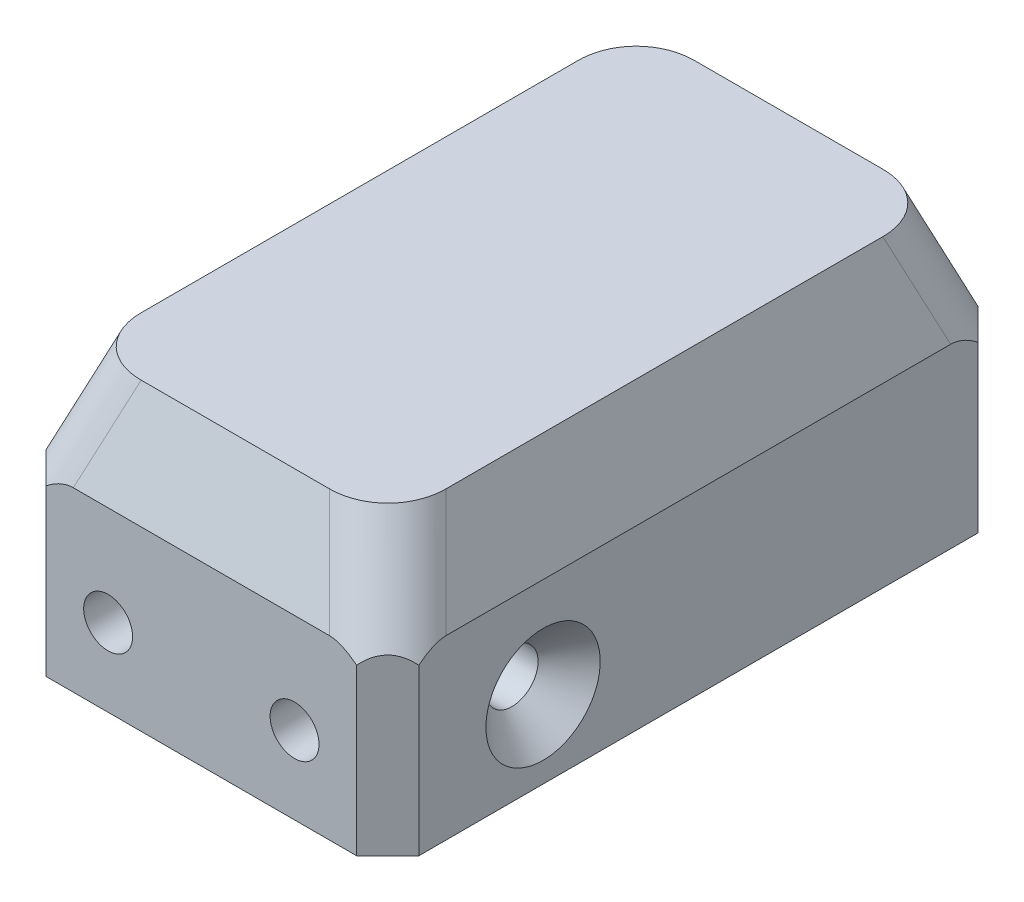
SolidWorks part; units mm, degrees
ref_plane "Front Plane" through (0, 0, 0) normal (0, 0, 1) x (1, 0, 0)
ref_plane "Top Plane" through (0, 0, 0) normal (0, 1, 0) x (1, 0, 0)
ref_plane "Right Plane" through (0, 0, 0) normal (1, 0, 0) x (0, 0, -1)
sketch "Sketch1" plane through (0, 0, 0) normal (0, 1, 0) x (1, 0, 0)
  line L0 (0, 12.7) -> (0, -12.7) construction
  line L1 (7.62, -12.7) -> (-7.62, -12.7)
  line L2 (7.62, -12.7) -> (7.62, 12.7)
  line L3 (7.62, 12.7) -> (-7.62, 12.7)
  line L4 (-7.62, -12.7) -> (-7.62, 12.7)
  line L5 (7.62, -12.7) -> (-7.62, 12.7) construction
  line L6 (7.62, 12.7) -> (-7.62, -12.7) construction
  line L7 (0, 0) -> (0, 12.7) construction
  line L8 (-7.62, 6.35) -> (7.62, 6.35) construction
  line L9 (0, 0) -> (0, -12.7) construction
  line L10 (-7.62, -6.35) -> (7.62, -6.35) construction
  line L11 (-7.62, 0) -> (7.62, 0) construction
  line L12 (3.81, 2.54) -> (-3.81, 2.54)
  line L13 (3.81, 2.54) -> (3.81, 10.16)
  line L14 (3.81, 10.16) -> (-3.81, 10.16)
  line L15 (-3.81, 2.54) -> (-3.81, 10.16)
  line L16 (3.81, 2.54) -> (-3.81, 10.16) construction
  line L17 (3.81, 10.16) -> (-3.81, 2.54) construction
  line L18 (3.81, -10.16) -> (-3.81, -10.16)
  line L19 (-3.81, -2.54) -> (-3.81, -10.16)
  line L20 (3.81, -2.54) -> (-3.81, -2.54)
  line L21 (3.81, -2.54) -> (3.81, -10.16)
  point P0 (0, 0)
  point P9 (0, 6.35)
  point P12 (0, 6.35)
  point P15 (0, -6.35)
  dimension "D1" = 25.4
  dimension "D2" = 15.24
  dimension "D3" = 7.62
  dimension "D4" = 7.62
extrude "Boss-Extrude1" add sketch "Sketch1" along normal blind 6.35 contours L2 L1 L4 L3 | L18 L19 L20 L21 | L13 L12 L15 L14
sketch "Sketch2" plane through (7.62, 0, 0) normal (1, 0, 0) x (0, 0, -1)
  line L0 (-12.7, 0) -> (0, 0) construction
  line L1 (-6.35, 0) -> (-6.35, 6.35) construction
  line L2 (-12.7, 6.35) -> (12.7, 6.35) construction
  line L3 (0, 0) -> (0, 6.35) construction
  circle A0 centre (-6.35, 3.175) radius 1.0668
  circle A1 centre (6.35, 3.175) radius 1.0668
  dimension "D1" = 2.1336
extrude "Cut-Extrude1" cut sketch "Sketch2" against normal through all
sketch "Sketch3" plane through (0, 0, 12.7) normal (0, 0, 1) x (1, 0, 0)
  line L0 (0, 0) -> (0, 6.35) construction
  line L1 (7.62, 6.35) -> (-7.62, 6.35) construction
  line L2 (-7.62, 6.35) -> (0, 6.35) construction
  line L3 (-3.81, 6.35) -> (-3.81, 0) construction
  line L4 (-3.81, 0) -> (0, 0) construction
  line L5 (-1.905, 0) -> (-1.905, 6.35) construction
  line L6 (-7.62, 4.2418) -> (-7.62, 2.1082) construction
  line L7 (-7.62, 4.2418) -> (-7.62, 2.1082) construction
  circle A0 centre (-1.905, 3.175) radius 1.0668
  circle A1 centre (1.905, 3.175) radius 1.0668
  dimension "D1" = 2.1336
extrude "Cut-Extrude2" cut sketch "Sketch3" against normal through all
sketch "Sketch4" plane through (0, 6.35, 0) normal (0, 1, 0) x (1, 0, 0)
  line L0 (-3.81, 2.54) -> (-3.81, -2.54)
  line L1 (-3.81, -2.54) -> (3.81, -2.54)
  line L2 (3.81, -2.54) -> (3.81, 2.54)
  line L3 (3.81, 2.54) -> (-3.81, 2.54)
extrude "Boss-Extrude2" add sketch "Sketch4" against normal up to surface (6.35 mm away) up to face at (0, 0, 6.35)
sketch "Sketch5" plane through (0, 0, 0) normal (0, -1, 0) x (1, 0, 0)
  line L0 (-3.81, -6.35) -> (-7.62, -6.35) construction
  line L1 (-3.81, -2.54) -> (-3.81, -10.16) construction
  line L2 (-7.62, 12.7) -> (-7.62, -12.7) construction
  line L3 (-3.81, -3.4925) -> (-3.81, -9.2075) construction
  point P9 (-3.81, -6.35)
  dimension "D1" = 5.715
sketch "Sketch6" plane through (0, 0, 12.7) normal (0, 0, 1) x (1, 0, 0)
  circle A0 centre (3.81, 3.175) radius 1
  circle A1 centre (-3.81, 3.175) radius 1
  dimension "D1" = 2
  dimension "D2" = 2
extrude "Cut-Extrude3" cut sketch "Sketch6" against normal up to surface (2.54 mm away) up to face at (-0.8382, 3.175, 10.16)
sketch "Sketch7" plane through (0, 0, 12.7) normal (0, 0, 1) x (1, 0, 0)
  line L0 (3.81, 4.175) -> (3.81, 2.175) construction
  arc A0 (2.8937, 3.5756) -> (2.8937, 2.7744) centre (1.905, 3.175) ccw construction
  arc A1 (-2.8937, 2.7744) -> (-2.8937, 3.5756) centre (-1.905, 3.175) ccw construction
  arc A2 (2.8937, 3.5756) -> (2.8937, 2.7744) centre (1.905, 3.175) ccw
  arc A3 (-2.8937, 2.7744) -> (-2.8937, 3.5756) centre (-1.905, 3.175) ccw
  arc A4 (2.8937, 3.5756) -> (2.8937, 2.7744) centre (3.81, 3.175) ccw
  arc A5 (-2.8937, 2.7744) -> (-2.8937, 3.5756) centre (-3.81, 3.175) ccw
extrude "Boss-Extrude3" add sketch "Sketch7" against normal up to surface (2.54 mm away) up to face at (0, 3.175, 10.16)
sketch "Sketch8" plane through (0, 0, -12.7) normal (0, 0, -1) x (-1, 0, 0)
  circle A0 centre (3.81, 3.175) radius 1 construction
  circle A1 centre (-3.81, 3.175) radius 1 construction
  circle A2 centre (3.81, 3.175) radius 1
  circle A3 centre (-3.81, 3.175) radius 1
extrude "Cut-Extrude4" cut sketch "Sketch8" against normal up to surface (2.54 mm away) up to face at (-0.8382, 3.175, -10.16)
sketch "Sketch9" plane through (0, 0, -12.7) normal (0, 0, -1) x (-1, 0, 0)
  line L0 (-3.81, 2.175) -> (-3.81, 4.175) construction
  line L1 (3.81, 2.175) -> (3.81, 4.175) construction
  arc A0 (2.8937, 3.5756) -> (2.8937, 2.7744) centre (1.905, 3.175) ccw construction
  arc A1 (-2.8937, 2.7744) -> (-2.8937, 3.5756) centre (-1.905, 3.175) ccw construction
  arc A2 (2.8937, 3.5756) -> (2.8937, 2.7744) centre (1.905, 3.175) ccw
  arc A3 (-2.8937, 2.7744) -> (-2.8937, 3.5756) centre (-1.905, 3.175) ccw
  arc A4 (-2.8937, 2.7744) -> (-2.8937, 3.5756) centre (-3.81, 3.175) ccw
  arc A5 (2.8937, 3.5756) -> (2.8937, 2.7744) centre (3.81, 3.175) ccw
extrude "Boss-Extrude4" add sketch "Sketch9" against normal up to surface (2.54 mm away) up to face at (0, 3.175, -10.16)
sketch "Sketch10" plane through (-7.62, 0, 0) normal (-1, 0, 0) x (0, 0, 1)
  circle A0 centre (-6.35, 3.175) radius 1.0668 construction
  circle A1 centre (-6.35, 3.175) radius 1.0668
extrude "Boss-Extrude5" add sketch "Sketch10" against normal up to surface (15.24 mm away) up to face at (7.62, 3.175, 5.2832)
sketch "Sketch11" plane through (0, 0, 0) normal (0, -1, 0) x (1, 0, 0)
  line L0 (3.81, -10.16) -> (-3.81, -10.16) construction
  line L1 (3.81, -2.54) -> (3.81, -10.16) construction
  line L2 (3.81, -2.54) -> (-3.81, -2.54) construction
  line L3 (-3.81, -2.54) -> (-3.81, -10.16) construction
  line L4 (3.81, -10.16) -> (-3.81, -10.16)
  line L5 (3.81, -2.54) -> (3.81, -10.16)
  line L6 (3.81, -2.54) -> (-3.81, -2.54)
  line L7 (-3.81, -2.54) -> (-3.81, -10.16)
extrude "Boss-Extrude6" add sketch "Sketch11" against normal up to surface (6.35 mm away) up to face at (0, 6.35, -6.35)
sketch "Sketch13" plane through (0, 6.35, 0) normal (0, 1, 0) x (1, 0, 0)
  line L0 (-15.1122, 3.7944) -> (-15.0451, -2.0493) construction
  line L1 (-15.06, 6.2006) -> (-15.06, 9.3807) construction
  line L2 (-3.81, -9.272) -> (-3.81, -3.428)
  line L4 (-3.81, -2.54) -> (-3.81, -10.16) construction
  line L5 (-3.81, -3.428) -> (-3.81, -1.0217) construction
  line L6 (-3.81, -1.0217) -> (-3.81, 2.1584) construction
  line L7 (-3.81, -2.1647) -> (-3.81, 3.3014)
  line L8 (-3.81, -2.1647) -> (3.81, -2.1647)
  line L9 (3.81, -2.1647) -> (3.81, 3.3014)
  line L10 (3.81, 3.3014) -> (-3.81, 3.3014)
  point P7 (-3.81, -6.35)
  point P10 (-3.81, -6.35)
  point P15 (-3.81, 0.5683)
  dimension "D1" = 5.8436
  dimension "D2" = 3.1801
  dimension "D3" = 2.4063
  dimension "D4" = 2.4063
  dimension "D5" = 1.143
extrude "Cut-Extrude5" cut sketch "Sketch13" against normal through all contours L9 L10 L7 L8 region at (0, 6.35, -0.5683)
fillet "Fillet1" radius 1.27 4 edges at (3.81, 3.175, 2.1647) (-3.81, 3.175, 2.1647) (-3.81, 3.175, 2.54) (3.81, 3.175, 2.54) conic rho 0.5
sketch "Sketch15" plane through (0, 6.35, 0) normal (0, 1, 0) x (1, 0, 0)
  line L0 (-2.54, -2.1647) -> (-2.54, -2.54)
  line L1 (-2.54, -2.54) -> (2.54, -2.54)
  line L2 (2.54, -2.54) -> (2.54, -2.1647)
  line L3 (2.54, -2.1647) -> (-2.54, -2.1647)
extrude "Cut-Extrude6" cut sketch "Sketch15" against normal through all
sketch "Sketch16" plane through (0, 0, 10.16) normal (0, 0, 1) x (1, 0, 0)
  line L1 (-3.81, 2.175) -> (-3.81, 4.175)
  line L2 (-3.81, 2.175) -> (-3.81, 4.175)
  line L3 (3.81, 4.175) -> (3.81, 2.175)
  line L4 (3.81, 4.175) -> (3.81, 2.175)
  arc A1 (-3.81, 4.175) -> (-3.81, 2.175) centre (-3.81, 3.175) ccw
  arc A2 (-3.81, 4.175) -> (-3.81, 2.175) centre (-3.81, 3.175) ccw
  arc A3 (3.81, 2.175) -> (3.81, 4.175) centre (3.81, 3.175) ccw
  arc A4 (3.81, 2.175) -> (3.81, 4.175) centre (3.81, 3.175) ccw
  dimension "D1" = 0
  dimension "D2" = 0
extrude "Cut-Extrude7" cut sketch "Sketch16" against normal blind 1.905
sketch "Sketch17" plane through (0, 6.35, 0) normal (0, 1, 0) x (1, 0, 0)
  line L0 (-3.81, -0.8947) -> (-3.81, -3.81) construction
  line L1 (-3.81, -3.81) -> (3.81, -3.81) construction
  line L2 (3.81, -3.81) -> (3.81, -0.8947) construction
  line L3 (3.81, -0.8947) -> (-3.81, -0.8947) construction
  line L4 (-2.54, -2.1647) -> (2.54, -2.1647)
  line L5 (2.54, -2.1647) -> (3.81, -2.1647)
  line L6 (3.81, -2.1647) -> (3.81, 3.3014)
  line L7 (3.81, 3.3014) -> (-3.81, 3.3014)
  line L8 (-3.81, 3.3014) -> (-3.81, -2.1647)
  line L9 (-3.81, -2.1647) -> (-2.54, -2.1647)
  line L10 (-4.1853, -2.54) -> (-2.54, -2.54)
  line L11 (-2.54, -2.54) -> (2.54, -2.54)
  line L12 (2.54, -2.54) -> (4.1853, -2.54)
  line L13 (4.1853, -2.54) -> (4.1853, 3.6767)
  line L14 (4.1853, 3.6767) -> (-4.1853, 3.6767)
  line L15 (-4.1853, 3.6767) -> (-4.1853, -2.54)
extrude "Boss-Extrude7" add sketch "Sketch17" along normal blind 3.175
sketch "Sketch18" plane through (0, 9.525, 0) normal (0, 1, 0) x (1, 0, 0)
  line L0 (-4.1853, 0.5683) -> (-3.81, 0.5683) construction
  line L1 (-3.81, 3.3014) -> (-3.81, -2.1647) construction
  line L2 (-3.81, 0.5683) -> (-4.826, 0.5683) construction
  line L3 (-4.8203, 4.3117) -> (-4.8203, -3.175)
  line L4 (-4.1853, 3.6767) -> (-4.1853, -2.54)
  line L5 (-4.1853, -2.54) -> (4.1853, -2.54)
  line L6 (4.1853, -2.54) -> (4.1853, 3.6767)
  line L7 (4.1853, 3.6767) -> (-4.1853, 3.6767)
  line L8 (-4.1853, 3.6767) -> (-4.1853, -2.54)
  line L9 (-4.1853, -2.54) -> (4.1853, -2.54)
  line L10 (4.1853, -2.54) -> (4.1853, 3.6767)
  line L11 (4.1853, 3.6767) -> (-4.1853, 3.6767)
  line L12 (-4.8203, -3.175) -> (4.8203, -3.175)
  line L13 (4.8203, -3.175) -> (4.8203, 4.3117)
  line L14 (4.8203, 4.3117) -> (-4.8203, 4.3117)
  dimension "D2" = 1.016
  dimension "D1" = 0
  dimension "D3" = 0.635
extrude "Boss-Extrude8" add sketch "Sketch18" against normal blind 3.175
sketch "Sketch19" plane through (0, 9.525, 0) normal (0, 1, 0) x (1, 0, 0)
  line L4 (4.8203, 4.3117) -> (-4.8203, 4.3117)
  line L5 (-4.8203, 4.3117) -> (-4.8203, -3.175)
  line L6 (-4.8203, -3.175) -> (4.8203, -3.175)
  line L7 (4.8203, -3.175) -> (4.8203, 4.3117)
  line L8 (4.8203, 4.3117) -> (-4.8203, 4.3117)
  line L9 (-4.8203, 4.3117) -> (-4.8203, -3.175)
  line L10 (-4.8203, -3.175) -> (4.8203, -3.175)
  line L11 (4.8203, -3.175) -> (4.8203, 4.3117)
  dimension "D1" = 0
extrude "Boss-Extrude9" add sketch "Sketch19" along normal blind 1.524
sketch "Sketch20" plane through (0, 0, 0) normal (0, -1, 0) x (1, 0, 0)
  line L0 (-3.81, 10.16) -> (-3.81, -3.3014)
  line L1 (-3.81, -3.3014) -> (3.81, -3.3014)
  line L2 (3.81, -3.3014) -> (3.81, 10.16)
  line L3 (3.81, 10.16) -> (-3.81, 10.16)
extrude "Cut-Extrude8" cut sketch "Sketch20" against normal up to surface (6.35 mm away) up to face at (-1.2337, 6.35, 2.6266)
fillet "Fillet2" radius 0.635 3 edges at (4.8203, 6.35, -0.5683) (0, 6.35, -4.3117) (-4.8203, 6.35, -0.5683) conic rho 0.5
sketch "Sketch22" plane through (0, 0, -10.16) normal (0, 0, -1) x (-1, 0, 0)
  circle A0 centre (3.81, 3.175) radius 1 construction
  circle A1 centre (-3.81, 3.175) radius 1 construction
  circle A2 centre (3.81, 3.175) radius 1
  circle A3 centre (-3.81, 3.175) radius 1
extrude "Cut-Extrude9" cut sketch "Sketch22" against normal up to surface (6.8586 mm away) up to face at (0, 4.7625, -3.3014)
chamfer "Chamfer1" distance 1.27 angle 45 1 edges
sketch "Sketch23" plane through (0, 11.049, 0) normal (0, 1, 0) x (1, 0, 0)
  line L0 (-7.62, -11.43) -> (-6.35, -12.7)
  line L1 (6.35, -12.7) -> (7.62, -11.43)
  line L2 (-6.35, 12.7) -> (-7.62, 11.43)
  line L3 (7.62, 11.43) -> (6.35, 12.7)
  line L4 (7.62, 12.7) -> (-7.62, 12.7)
  line L5 (-7.62, 12.7) -> (-7.62, -12.7)
  line L6 (-7.62, -12.7) -> (7.62, -12.7)
  line L7 (7.62, -12.7) -> (7.62, 12.7)
  line L8 (6.35, 12.7) -> (-6.35, 12.7)
  line L9 (-7.62, 11.43) -> (-7.62, -11.43)
  line L10 (-6.35, -12.7) -> (6.35, -12.7)
  line L11 (7.62, -11.43) -> (7.62, 11.43)
  line L12 (-4.8203, 4.3117) -> (-4.8203, -3.175)
  line L13 (-4.8203, -3.175) -> (4.8203, -3.175)
  line L14 (4.8203, -3.175) -> (4.8203, 4.3117)
  line L15 (4.8203, 4.3117) -> (-4.8203, 4.3117)
  dimension "D1" = 0
extrude "Boss-Extrude11" add sketch "Sketch23" against normal up to surface (4.699 mm away) up to face at (0, 6.35, 0)
chamfer "Chamfer2" distance 0.254 angle 45 1 edges at (0, 6.35, 3.175)
chamfer "Chamfer3" distance 3.81 angle 20 4 edges at (0, 11.049, 12.7) (-7.62, 11.049, 0) (0, 11.049, -12.7) (7.62, 11.049, 0) first distance on face at (4.81, 3.175, 12.7) first distance on face at (-7.62, 3.175, 5.2832) first distance on face at (-4.81, 3.175, -12.7) first distance on face at (7.62, 3.175, 5.2832)
fillet "Fillet3" radius 2.54 4 edges at (6.6091, 10.0163, 11.6891) (-6.6091, 10.0163, 11.6891) (6.6091, 10.0163, -11.6891) (-6.6091, 10.0163, -11.6891)
chamfer "Chamfer4" distance 1.27 angle 45 2 edges at (7.62, 3.175, 5.2832) (-7.62, 3.175, 5.2832)
sketch "Sketch24" plane through (0, 6.35, 0) normal (0, 1, 0) x (1, 0, 0)
  line L3 (-7.62, 12.7) -> (-7.62, 11.43)
  line L4 (-7.62, 11.43) -> (-6.35, 12.7)
  line L5 (-6.35, 12.7) -> (-7.62, 12.7)
  line L6 (-7.62, 12.7) -> (-7.62, 11.43)
  line L7 (-7.62, 11.43) -> (-6.35, 12.7)
  line L8 (-6.35, 12.7) -> (-7.62, 12.7)
  line L9 (7.62, 12.7) -> (6.35, 12.7)
  line L10 (6.35, 12.7) -> (7.62, 11.43)
  line L11 (7.62, 11.43) -> (7.62, 12.7)
  line L12 (7.62, 12.7) -> (6.35, 12.7)
  line L13 (6.35, 12.7) -> (7.62, 11.43)
  line L14 (7.62, 11.43) -> (7.62, 12.7)
  line L15 (-7.62, -12.7) -> (-6.35, -12.7)
  line L16 (-6.35, -12.7) -> (-7.62, -11.43)
  line L17 (-7.62, -11.43) -> (-7.62, -12.7)
  line L18 (-7.62, -12.7) -> (-6.35, -12.7)
  line L19 (-6.35, -12.7) -> (-7.62, -11.43)
  line L20 (-7.62, -11.43) -> (-7.62, -12.7)
  line L21 (7.62, -12.7) -> (7.62, -11.43)
  line L22 (7.62, -11.43) -> (6.35, -12.7)
  line L23 (6.35, -12.7) -> (7.62, -12.7)
  line L24 (7.62, -12.7) -> (7.62, -11.43)
  line L25 (7.62, -11.43) -> (6.35, -12.7)
  line L26 (6.35, -12.7) -> (7.62, -12.7)
  dimension "D1" = 0
  dimension "D2" = 0
  dimension "D3" = 0
  dimension "D4" = 0
extrude "Cut-Extrude10" cut sketch "Sketch24" against normal through all
sketch "Sketch25" plane through (0, 0, -12.7) normal (0, 0, -1) x (-1, 0, 0)
  circle A0 centre (3.81, 3.175) radius 1 construction
  circle A1 centre (-3.81, 3.175) radius 1 construction
  circle A2 centre (3.81, 3.175) radius 1
  circle A3 centre (-3.81, 3.175) radius 1
extrude "Cut-Extrude11" cut sketch "Sketch25" against normal through all
